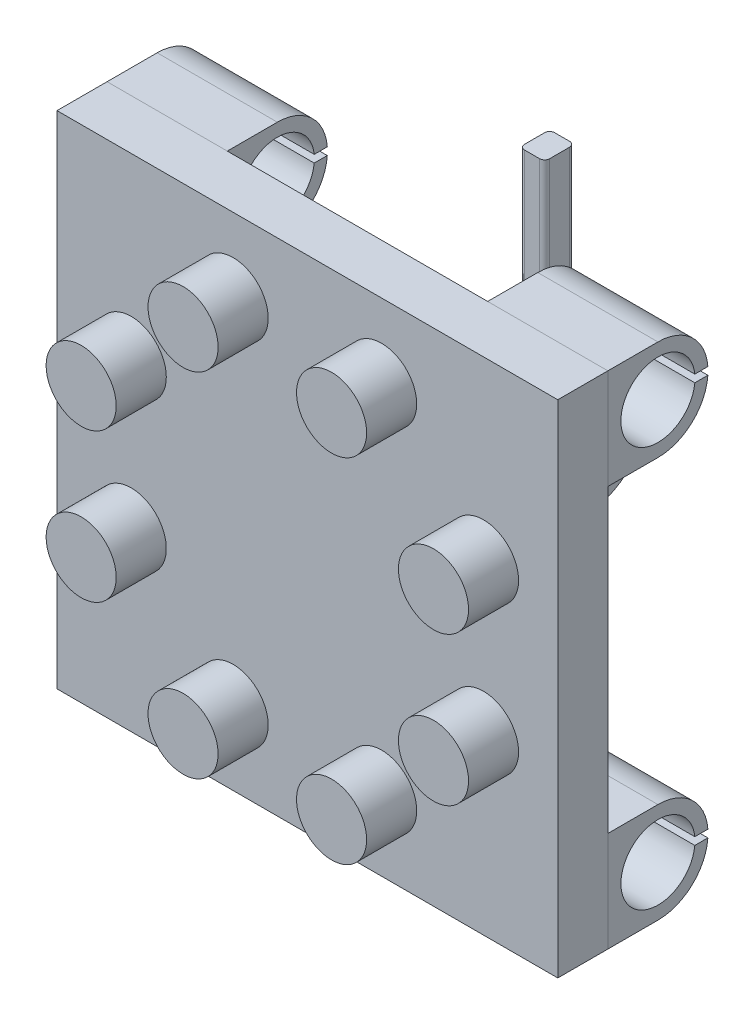
SolidWorks part; units mm, degrees
ref_plane "Plano frontal" through (0, 0, 0) normal (0, 0, 1) x (1, 0, 0)
ref_plane "Plano superior" through (0, 0, 0) normal (0, 1, 0) x (1, 0, 0)
ref_plane "Plano direito" through (0, 0, 0) normal (1, 0, 0) x (0, 0, -1)
sketch "Esboço1" plane through (0, 0, 0) normal (0, 0, 1) x (1, 0, 0)
  line L1 (-25.8743, 34.174) -> (-25.8743, -39.4705) construction
  line L2 (-25.8743, 21.9595) -> (37.4155, 21.9595) construction
  line L3 (24.1257, -28.0405) -> (24.1257, 21.9595) construction
  line L4 (-25.8743, 21.9595) -> (-11.0487, 7.134) construction
  line L5 (-11.0487, 7.134) -> (9.3002, -13.2149) construction
  line L6 (9.3002, -13.2149) -> (24.1257, -28.0405) construction
  line L7 (-25.8743, -28.0405) -> (24.1257, 21.9595) construction
  line L9 (-25.8743, 21.9595) -> (24.1257, 21.9595)
  line L10 (-25.8743, 21.9595) -> (-25.8743, -28.0405)
  line L11 (-25.8743, -28.0405) -> (24.1257, -28.0405)
  line L12 (24.1257, 21.9595) -> (24.1257, -28.0405)
  dimension "D1" = 50
extrude "Ressalto-extrusão1" add sketch "Esboço1" along normal blind 10
sketch "Esboço2" plane through (0, 0, 10) normal (0, 0, 1) x (1, 0, 0)
  line L0 (-25.8743, -28.0405) -> (27.247, -28.0405) construction
  line L1 (-11.0487, 21.9595) -> (-11.0487, -28.0405) construction
  line L2 (24.1257, 21.9595) -> (-25.8743, 21.9595) construction
  line L3 (9.3002, 21.9595) -> (9.3002, -28.0405) construction
  line L4 (-25.8743, -28.0405) -> (-25.8743, 21.9595) construction
  line L5 (-25.8743, 7.134) -> (24.1257, 7.134) construction
  line L6 (24.1257, -28.0405) -> (24.1257, 21.9595) construction
  line L7 (-25.8743, -13.2149) -> (24.1257, -13.2149) construction
  circle A0 centre (-11.0487, 7.134) radius 7
  circle A3 centre (9.3002, -13.2149) radius 7
extrude "Ressalto-extrusão2" add sketch "Esboço2" along normal blind 10
mirror "Espelhar11" about plane through (-25.8743, 21.9595, 10) normal (1, 0, 0) of "Ressalto-extrusão2", "Ressalto-extrusão1"
mirror "Espelhar12" about plane through (-25.8743, -28.0405, 10) normal (0, 1, 0) of "Ressalto-extrusão2", "Ressalto-extrusão1"
mirror "Espelhar13" about plane through (-25.8743, -78.0405, 10) normal (-1, 0, 0) of "Espelhar12"
sketch "Esboço3" plane through (0, 0, 0) normal (0, 0, -1) x (-1, 0, 0)
  line L2 (-24.1257, -78.0405) -> (-0.1257, -78.0405)
  line L5 (-24.1257, -78.0405) -> (-24.1257, -58.0405)
  line L31 (-24.1257, -58.0405) -> (-0.1257, -58.0405)
  line L35 (-0.1257, -78.0405) -> (-0.1257, -58.0405)
  line L41 (51.8743, -78.0405) -> (75.8743, -78.0405)
  line L54 (51.8743, -78.0405) -> (51.8743, -58.0405)
  line L55 (51.8743, -58.0405) -> (75.8743, -58.0405)
  line L56 (75.8743, -78.0405) -> (75.8743, -58.0405)
  line L57 (51.8743, 1.9595) -> (75.8743, 1.9595)
  line L58 (51.8743, 1.9595) -> (51.8743, 21.9595)
  line L59 (51.8743, 21.9595) -> (75.8743, 21.9595)
  line L60 (75.8743, 1.9595) -> (75.8743, 21.9595)
  line L61 (-24.1257, 1.9595) -> (-0.1257, 1.9595)
  line L62 (-24.1257, 1.9595) -> (-24.1257, 21.9595)
  line L63 (-24.1257, 21.9595) -> (-0.1257, 21.9595)
  line L64 (-0.1257, 1.9595) -> (-0.1257, 21.9595)
  dimension "D1" = 24
  dimension "D2" = 20
extrude "Ressalto-extrusão3" add sketch "Esboço3" along normal blind 20 separate body
fillet "Filete3" radius 10 2 edges at (12.1257, -58.0405, -20) (12.1257, -78.0405, -20)
fillet "Filete4" radius 10 2 edges at (-63.8743, -58.0405, -20) (-63.8743, -78.0405, -20)
fillet "Filete5" radius 10 2 edges at (12.1257, 21.9595, -20) (12.1257, 1.9595, -20)
fillet "Filete6" radius 10 2 edges at (-63.8743, 21.9595, -20) (-63.8743, 1.9595, -20)
sketch "Esboço4" plane through (24.1257, 0, 0) normal (1, 0, 0) x (0, 0, -1)
  line L0 (20, -68.0405) -> (17.4, -68.0405) construction
  line L1 (0, -58.0405) -> (0, -78.0405) construction
  line L2 (10, -78.0405) -> (10, -58.0405) construction
  line L3 (10, 1.9595) -> (10, 21.9595) construction
  line L4 (20, 11.9595) -> (0, 11.9595) construction
  line L5 (0, 21.9595) -> (0, 1.9595) construction
  line L6 (16.8497, -68.0405) -> (0, -68.0405) construction
  line L11 (20.3514, -68.7905) -> (17.3619, -68.7905)
  line L12 (20.3514, -68.7905) -> (20.3514, -67.2905)
  line L13 (20.3514, -67.2905) -> (17.3619, -67.2905)
  line L15 (20.3514, 11.2095) -> (17.3619, 11.2095)
  line L16 (20.3514, 11.2095) -> (20.3514, 12.7095)
  line L17 (20.3514, 12.7095) -> (17.3619, 12.7095)
  arc A0 (17.3619, -67.2905) -> (17.3619, -68.7905) centre (10, -68.0405) ccw
  arc A2 (17.3619, 12.7095) -> (17.3619, 11.2095) centre (10, 11.9595) ccw
  point P25 (10, 11.9595)
  dimension "D1" = 14.8
  dimension "D2" = 1.5
extrude "Corte-extrusão1" cut sketch "Esboço4" against normal through all both and the other way through all
sketch "Esboço5" plane through (0, 0, 0) normal (0, 0, -1) x (-1, 0, 0)
  line L0 (75.8743, -28.0405) -> (-24.1257, -28.0405) construction
  line L1 (75.8743, -78.0405) -> (75.8743, 21.9595) construction
  line L2 (-24.1257, -78.0405) -> (-24.1257, 21.9595) construction
  line L3 (25.8743, -78.0405) -> (25.8743, 21.9595) construction
  line L4 (-24.1257, -78.0405) -> (75.8743, -78.0405) construction
  line L5 (-24.1257, 21.9595) -> (75.8743, 21.9595) construction
  line L6 (43.3743, -28.0405) -> (8.3743, -28.0405) construction
  line L7 (43.3743, -43.0405) -> (8.3743, -43.0405)
  line L8 (43.3743, -43.0405) -> (43.3743, -13.0405)
  line L9 (43.3743, -13.0405) -> (8.3743, -13.0405)
  line L10 (8.3743, -43.0405) -> (8.3743, -13.0405)
  line L11 (25.8743, -43.0405) -> (25.8743, -13.0405) construction
  point P20 (25.8743, -28.0405)
  point P21 (25.8743, -28.0405)
  dimension "D1" = 35
  dimension "D2" = 30
extrude "Ressalto-extrusão4" add sketch "Esboço5" along normal blind 50
sketch "Esboço6" plane through (-43.3743, 0, 0) normal (-1, 0, 0) x (0, 0, 1)
  line L0 (-50, -28.0405) -> (0, -28.0405) construction
  line L1 (-50, -43.0405) -> (-50, -13.0405) construction
  line L2 (0, -78.0405) -> (0, 21.9595) construction
  line L3 (-25, -43.0405) -> (-25, -13.0405) construction
  line L4 (-50, -43.0405) -> (0, -43.0405) construction
  line L5 (-50, -13.0405) -> (0, -13.0405) construction
  line L6 (-25, -43.0405) -> (-50, -13.0405) construction
  line L7 (-25, -13.0405) -> (-50, -43.0405) construction
  circle A0 centre (-37.5, -28.0405) radius 11.5
  dimension "D1" = 23
sketch "Esboço7" plane through (0, -43.0405, 0) normal (0, -1, 0) x (1, 0, 0)
  line L0 (-25.8743, -50) -> (-25.8743, 0) construction
  line L1 (-8.3743, -50) -> (-43.3743, -50) construction
  line L2 (-8.3743, 0) -> (-43.3743, 0) construction
  line L3 (-25.8743, -50) -> (-32.8743, -50) construction
  line L4 (-25.8743, -50) -> (-18.8743, -50) construction
  line L5 (-8.3743, 0) -> (-8.3743, -50)
  line L6 (-18.8743, -50) -> (-8.3743, -50)
  line L7 (-43.3743, 0) -> (-43.3743, -50)
  line L8 (-32.8743, -50) -> (-43.3743, -50)
  arc A0 (-32.8743, -50) -> (-43.3743, 0) centre (-157.1719, -50) ccw
  arc A1 (-18.8743, -50) -> (-8.3743, 0) centre (105.4234, -50) cw
extrude "Corte-extrusão2" cut sketch "Esboço7" against normal through all both and the other way through all
extrude "Corte-extrusão3" cut sketch "Esboço6" against normal blind 15
sketch "Esboço8" plane through (-28.3743, 0, 0) normal (-1, 0, 0) x (0, 0, 1)
  circle A0 centre (-37.5, -28.0405) radius 5.25
  circle A1 centre (-37.5, -28.0405) radius 11.5 construction
  dimension "D1" = 10.5
extrude "Corte-extrusão4" cut sketch "Esboço8" against normal through all
fillet "Filete7" radius 10 2 edges at (-25.8743, -13.0405, -50) (-25.8743, -43.0405, -50)
sketch "Esboço9" plane through (0, -13.0405, 0) normal (0, 1, 0) x (1, 0, 0)
  line L0 (-148.4687, 37.8701) -> (-15.7518, 37.8701) construction
  line L1 (-27.3743, 40.8701) -> (-24.3743, 40.8701)
  line L2 (-28.3743, 39.8701) -> (-28.3743, 35.8701)
  line L3 (-27.3743, 34.8701) -> (-24.3743, 34.8701)
  line L4 (-23.3743, 39.8701) -> (-23.3743, 35.8701)
  line L5 (-28.3743, 37.8701) -> (-23.3743, 37.8701) construction
  line L6 (-25.8743, 50) -> (-25.8743, 23.4143) construction
  line L7 (-32.8743, 50) -> (-18.8743, 50) construction
  line L8 (-25.8743, 40.8701) -> (-25.8743, 34.8701) construction
  arc A0 (-28.3743, 35.8701) -> (-27.3743, 34.8701) centre (-27.3743, 35.8701) ccw
  arc A1 (-24.3743, 34.8701) -> (-23.3743, 35.8701) centre (-24.3743, 35.8701) ccw
  arc A2 (-24.3743, 40.8701) -> (-23.3743, 39.8701) centre (-24.3743, 39.8701) cw
  arc A3 (-27.3743, 40.8701) -> (-28.3743, 39.8701) centre (-27.3743, 39.8701) ccw
  point P19 (-23.3743, 34.8701)
  point P22 (-23.3743, 40.8701)
  point P25 (-28.3743, 40.8701)
  dimension "D3" = 1
  dimension "D1" = 5
  dimension "D2" = 6
extrude "Ressalto-extrusão5" add sketch "Esboço9" along normal blind 30
